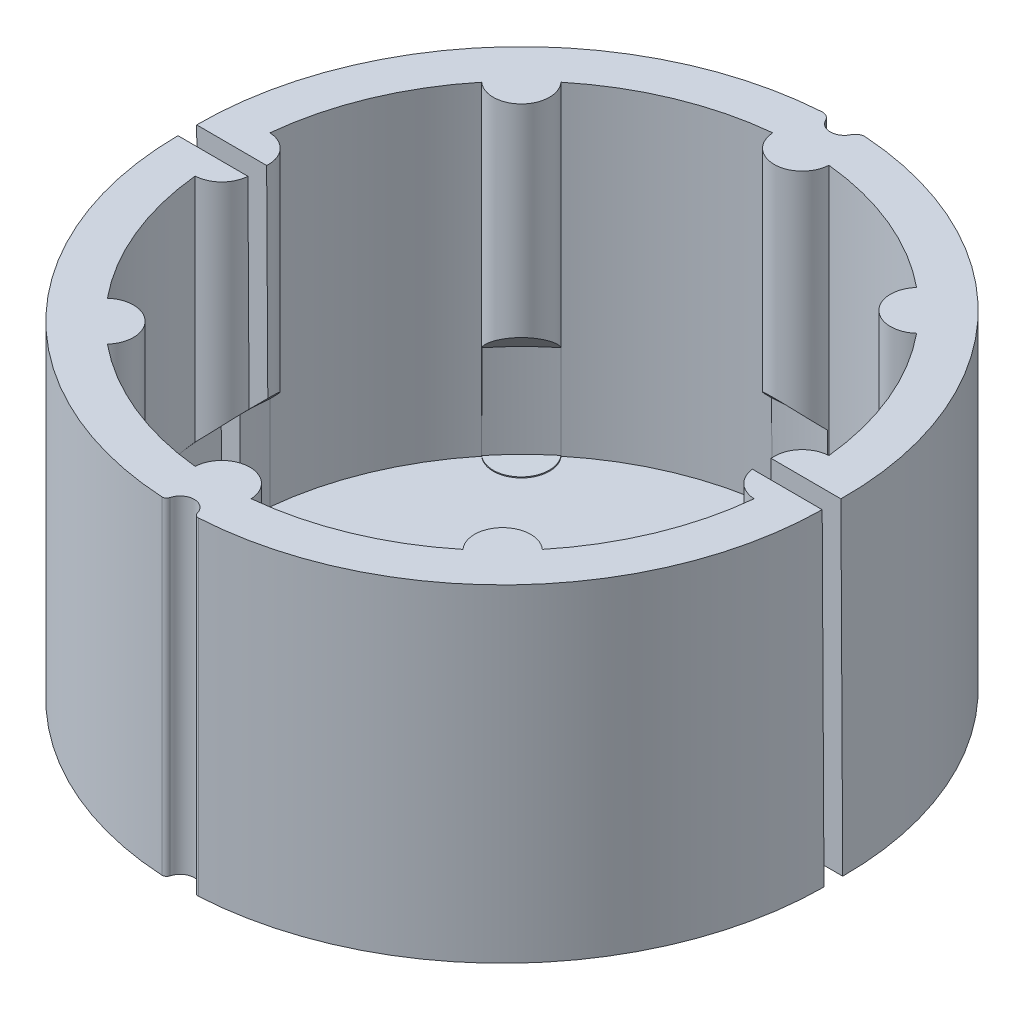
SolidWorks part; units mm, degrees
ref_plane "Front Plane" through (0, 0, 0) normal (0, 0, 1) x (1, 0, 0)
ref_plane "Top Plane" through (0, 0, 0) normal (0, 1, 0) x (1, 0, 0)
ref_plane "Right Plane" through (0, 0, 0) normal (1, 0, 0) x (0, 0, -1)
sketch "Sketch1" plane through (0, 0, 0) normal (0, 1, 0) x (1, 0, 0)
  line L3 (0, 0.002) -> (0, 3.7877) construction
  line L4 (0, 3.7877) -> (2.417, 3.7877)
  line L5 (0, 3.7877) -> (-2.417, 3.7877)
  arc A0 (1.9642, -34.442) -> (34.1982, 4.5552) centre (0, 0.002) ccw
  arc A2 (-2.417, 3.7877) -> (2.417, 3.7877) centre (0, 0.002) ccw
  circle A3 centre (0, 0.002) radius 34.5 construction
  arc A7 (-1.3541, 33.8562) -> (1.3541, 33.8562) centre (0, 34.5015) ccw
  arc A8 (34.1982, 4.5552) -> (2.3241, 34.4236) centre (0, 0.002) ccw
  arc A9 (-2.3241, 34.4236) -> (-34.1982, 4.5552) centre (0, 0.002) ccw
  arc A10 (-34.1982, 4.5552) -> (-1.9642, -34.442) centre (0, 0.002) ccw
  arc A11 (1.3541, 33.8562) -> (2.3241, 34.4236) centre (2.2568, 33.4259) cw
  arc A12 (-1.3541, 33.8562) -> (-2.3241, 34.4236) centre (-2.2568, 33.4259) ccw
  arc A13 (1.4518, -34.0686) -> (-1.4518, -34.0686) centre (0, -34.4457) ccw
  arc A14 (1.4518, -34.0686) -> (1.9642, -34.442) centre (1.9358, -33.9428) ccw
  arc A15 (-1.4518, -34.0686) -> (-1.9642, -34.442) centre (-1.9358, -33.9428) cw
  point P15 (1.4997, 34.4694)
  dimension "D2" = 4.834
  dimension "D3" = 4.4915
  dimension "D4" = 34.5
  dimension "D5" = 1
  dimension "D6" = 1.5
  dimension "D7" = 0.5
  dimension "D11" = 1.4997
sketch "Sketch2" plane through (0, 0, 0) normal (0, 1, 0) x (1, 0, 0)
  arc A16 (-23.2258, 18.9885) -> (-29.85, 2.9962) centre (0, 0) ccw
  circle A23 centre (0, 0) radius 27 construction
  arc A24 (-2.9962, 29.85) -> (2.9962, 29.85) centre (0, 30) ccw
  arc A25 (18.9885, 23.2258) -> (23.2258, 18.9885) centre (21.2132, 21.2132) ccw
  arc A26 (29.85, 2.9962) -> (29.85, -2.9962) centre (30, 0) ccw
  arc A27 (23.2258, -18.9885) -> (18.9885, -23.2258) centre (21.2132, -21.2132) ccw
  arc A28 (2.9962, -29.85) -> (-2.9962, -29.85) centre (0, -30) ccw
  arc A29 (-18.9885, -23.2258) -> (-23.2258, -18.9885) centre (-21.2132, -21.2132) ccw
  arc A30 (-29.85, -2.9962) -> (-29.85, 2.9962) centre (-30, 0) ccw
  arc A31 (-23.2258, 18.9885) -> (-18.9885, 23.2258) centre (-21.2132, 21.2132) ccw
  arc A32 (-2.9962, 29.85) -> (-18.9885, 23.2258) centre (0, 0) ccw
  arc A33 (18.9885, 23.2258) -> (2.9962, 29.85) centre (0, 0) ccw
  arc A34 (29.85, 2.9962) -> (23.2258, 18.9885) centre (0, 0) ccw
  arc A35 (23.2258, -18.9885) -> (29.85, -2.9962) centre (0, 0) ccw
  arc A36 (2.9962, -29.85) -> (18.9885, -23.2258) centre (0, 0) ccw
  arc A37 (-18.9885, -23.2258) -> (-2.9962, -29.85) centre (0, 0) ccw
  arc A38 (-29.85, -2.9962) -> (-23.2258, -18.9885) centre (0, 0) ccw
  dimension "D1" = 8
  dimension "D2" = 60
  dimension "D3" = 54
extrude "Boss-Extrude1" add sketch "Sketch1" along normal blind 35 contours A10 A0 A8 A7 A9 A2 L5 L4 region at (2.2155, 0, 33.5591)
extrude "Cut-Extrude2" cut sketch "Sketch2" along normal through all
extrude "Boss-Extrude2" add sketch "Sketch2<2>" along normal blind 0.4
sketch "Sketch2<2>" plane through (0, 0, 0) normal (0, 1, 0) x (1, 0, 0) same geometry as "Sketch2"
ref_plane "Plane1" through (-0.0002, -0.0005, 0.0829) normal (-0.0028, -0.0054, 1) x (1, 0, 0.0028)
sketch "Sketch3" plane through (-0.0002, -0.0005, 0.0829) normal (-0.0028, -0.0054, 1) x (1, 0, 0.0028)
  line L0 (0, 0) -> (0, 0.4) construction
  line L1 (0, 0.4) -> (30, 0.4)
  line L2 (30, 0.4) -> (30, 10.4)
  line L3 (30, 10.4) -> (20.9286, 19.4714)
  line L5 (0, 0.4) -> (0, 5.4)
  line L6 (0, 5.4) -> (20.9286, 19.4714)
  dimension "D1" = 225
  dimension "D2" = 30
  dimension "D3" = 10
  dimension "D4" = 12.829
  dimension "D5" = 0.4
  dimension "D6" = 5
revolve "Cut-Revolve6" cut sketch "Sketch3" angle 360 about L5
ref_plane "Plane2" through (0, 35, 0) normal (0, 1, 0) x (1, 0, 0)
sketch "Sketch5" plane through (0, 35, 0) normal (0, 1, 0) x (1, 0, 0)
  line L0 (-34.4995, -0.1783) -> (34.4995, -0.1783)
  arc A2 (-2.3241, 34.4236) -> (-1.9642, -34.442) centre (0, 0.002) ccw construction
  arc A3 (1.9642, -34.442) -> (2.3241, 34.4236) centre (0, 0.002) ccw construction
split "Split1" trim tools "Plane1" bodies to split 109 resulting bodies 112 113
move or copy body "Body-Move/Copy1" bodies to move or copy 113 copy no translate (0, 0, -2)
equation "\"2.5.00mm\"=3"
